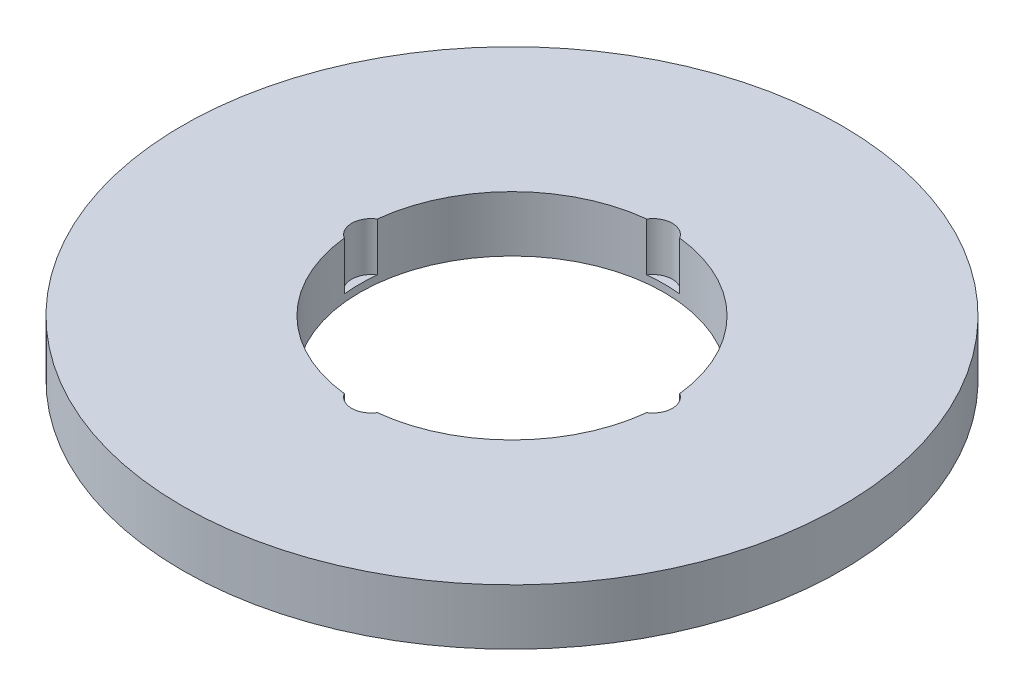
SolidWorks part; units mm, degrees
ref_plane "Front Plane" through (0, 0, 0) normal (0, 0, 1) x (1, 0, 0)
ref_plane "Top Plane" through (0, 0, 0) normal (0, 1, 0) x (1, 0, 0)
ref_plane "Right Plane" through (0, 0, 0) normal (1, 0, 0) x (0, 0, -1)
sketch "Sketch1" plane through (0, 0, 0) normal (0, 1, 0) x (1, 0, 0)
  circle A0 centre (0, 0) radius 65
  dimension "FLANGE_OD" = 130
extrude "Boss-Extrude1" add sketch "Sketch1" along normal blind 11
sketch "Sketch2" plane through (0, 0, 0) normal (0, 1, 0) x (1, 0, 0)
  circle A0 centre (0, 0) radius 30
  dimension "BORE_D" = 60
extrude "Cut-Extrude1" cut sketch "Sketch2" along normal through all
sketch "Sketch3" plane through (0, 11, 0) normal (0, 1, 0) x (1, 0, 0)
  circle A0 centre (0, 0) radius 27.7728 construction
  circle A1 centre (-27.7728, 0) radius 3.8472
  dimension "BOLT_D" = 7.6945
  dimension "BOLT_PCD" = 55.5455
extrude "Cut-Extrude2" cut sketch "Sketch3" against normal blind 9.5596
pattern_circular "CirPattern1" count 4 over 360 about axis through (0, 0, 0) along (0, 1, 0) of "Cut-Extrude2"
